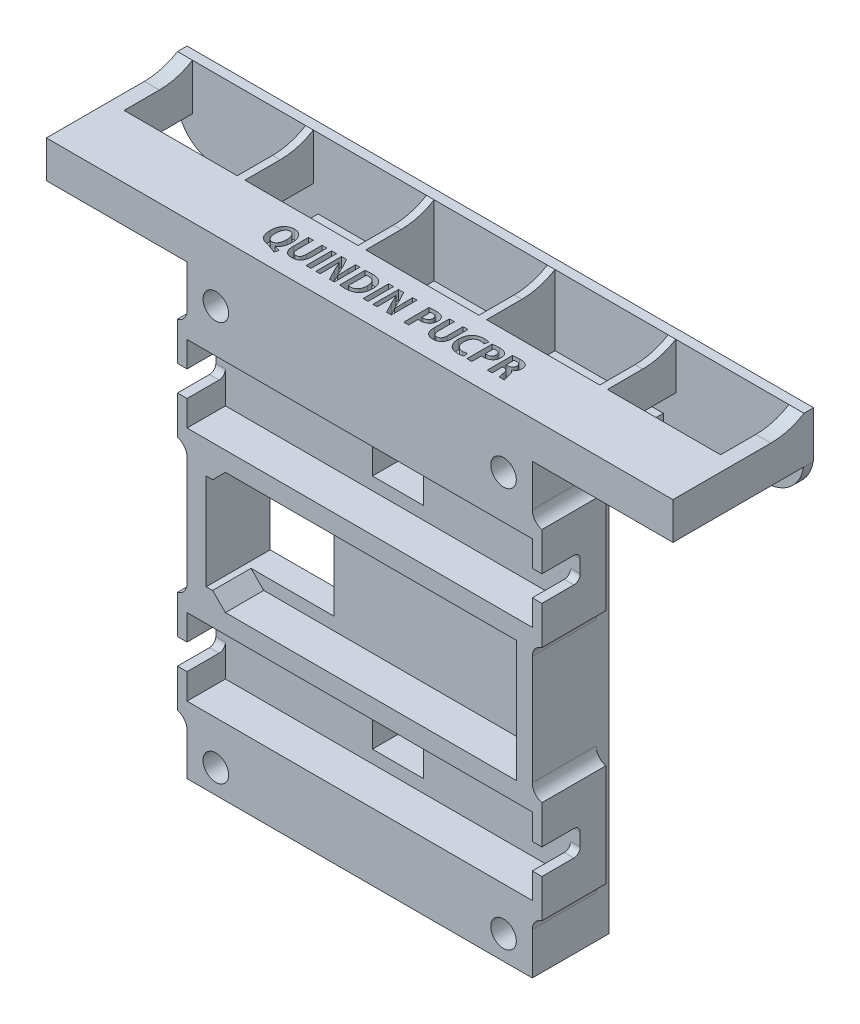
SolidWorks part; units mm, degrees
material "ABS"
ref_plane "Plano frontal" through (0, 0, 0) normal (0, 0, 1) x (1, 0, 0)
ref_plane "Plano superior" through (0, 0, 0) normal (0, 1, 0) x (1, 0, 0)
ref_plane "Plano direito" through (0, 0, 0) normal (1, 0, 0) x (0, 0, -1)
sketch "Esboço1" plane through (0, 0, 0) normal (0, 0, 1) x (1, 0, 0)
  line L0 (-22.1231, 28.35) -> (-22.1231, 2.85) construction
  line L2 (-26.6231, 32.1) -> (-26.6231, 23.6)
  line L3 (-26.6231, -37.9) -> (27.3769, -37.9)
  line L4 (27.3769, 32.1) -> (27.3769, 23.6)
  line L5 (-27.3795, 37.9037) -> (27.3769, -37.9) construction
  line L6 (-26.6231, -37.9) -> (26.6205, 37.8962) construction
  line L7 (-22.1231, 2.85) -> (22.8769, 2.85) construction
  line L8 (22.8769, -34.15) -> (22.8769, -8.65) construction
  line L9 (22.8769, -8.65) -> (-22.1231, -8.65) construction
  line L10 (0.3769, -37.9) -> (0.3769, 37.9) construction
  line L11 (27.3769, 32.1) -> (49.3769, 32.1)
  line L12 (49.3769, 32.1) -> (49.3769, 37.9)
  line L13 (-48.6231, 37.9) -> (49.3769, 37.9)
  line L14 (-48.6231, 37.9) -> (-48.6231, 32.1)
  line L15 (-48.6231, 32.1) -> (-26.6231, 32.1)
  line L33 (27.3769, -29.4) -> (27.3769, -37.9)
  line L35 (-26.6231, -37.9) -> (-26.6231, -29.4)
  line L38 (-28.1231, 15.6) -> (-26.6231, 15.6) construction
  line L39 (-26.6231, -13.4) -> (-28.1231, -13.4)
  line L41 (-26.6231, -29.4) -> (-28.1231, -29.4)
  line L42 (-28.1231, -13.4) -> (-28.1231, -29.4)
  line L43 (-26.6231, 23.6) -> (-28.1231, 23.6)
  line L45 (-26.6231, 7.6) -> (-28.1231, 7.6)
  line L46 (-28.1231, 23.6) -> (-28.1231, 7.6)
  line L47 (27.3769, -29.4) -> (28.8769, -29.4)
  line L48 (-28.1231, -21.4) -> (-26.6231, -21.4) construction
  line L49 (27.3769, -13.4) -> (28.8769, -13.4)
  line L50 (28.8769, -13.4) -> (28.8769, -29.4)
  line L51 (28.8769, 15.6) -> (27.3769, 15.6) construction
  line L52 (28.8769, 23.6) -> (28.8769, 7.6)
  line L53 (27.3769, 7.6) -> (28.8769, 7.6)
  line L54 (27.3769, 23.6) -> (28.8769, 23.6)
  line L55 (-26.6231, 7.6) -> (-26.6231, -13.4)
  line L56 (27.3769, -13.4) -> (27.3769, 7.6)
  line L59 (-48.6231, 32.1) -> (-48.6231, 46.1) construction
  line L60 (49.3769, 32.1) -> (49.3769, 46.1) construction
  circle A0 centre (-22.1231, 28.35) radius 2
  circle A1 centre (22.8769, 28.35) radius 2
  circle A2 centre (22.8769, -34.15) radius 2
  circle A3 centre (-22.1231, -34.15) radius 2
  point P0 (0, 0)
  dimension "D7" = 3.75
  dimension "D8" = 4
  dimension "D11" = 3.75
  dimension "D12" = 4
  dimension "D13" = 4
  dimension "D14" = 4
  dimension "D1" = 54
  dimension "D2" = 75.8
  dimension "D3" = 25.5
  dimension "D4" = 4.5
  dimension "D5" = 11.5
  dimension "D6" = 4.5
  dimension "D9" = 4.5
  dimension "D10" = 4.5
  dimension "D15" = 25.5
  dimension "D16" = 25.5
  dimension "D23" = 45
  dimension "D26" = 5.8
  dimension "D27" = 5.8
  dimension "D28" = 70
  dimension "D29" = 1.5
  dimension "D30" = 1.5
  dimension "D31" = 16
  dimension "D32" = 16
  dimension "D33" = 16.5
  dimension "D34" = 53.5
extrude "Ressalto-extrusão1" add sketch "Esboço1" along normal blind 10
sketch "Esboço7" plane through (0, 0, 0) normal (0, 0, -1) x (-1, 0, 0)
  line L0 (-0.3769, -37.9) -> (-0.3769, 37.9) construction
  line L1 (26.6231, -37.9) -> (-27.3769, -37.9) construction
  line L2 (-49.3769, 37.9) -> (48.6231, 37.9) construction
  line L3 (26.6231, 7.6) -> (26.6231, -13.4) construction
  line L4 (9.6231, 4.6) -> (23.6231, 4.6)
  line L5 (28.6231, 15.6) -> (-29.3769, 15.6) construction
  line L6 (9.6231, 4.6) -> (9.6231, -10.4)
  line L7 (-4.3769, 19.6) -> (3.6231, 19.6)
  line L8 (9.6231, -10.4) -> (23.6231, -10.4)
  line L9 (28.6231, -21.4) -> (-29.3769, -21.4) construction
  line L10 (23.6231, 4.6) -> (23.6231, -10.4)
  line L11 (-4.3769, 19.6) -> (-4.3769, 11.6)
  line L12 (-4.3769, 11.6) -> (3.6231, 11.6)
  line L13 (3.6231, 19.6) -> (3.6231, 11.6)
  line L14 (-4.3769, 19.6) -> (3.6231, 11.6) construction
  line L15 (-4.3769, 11.6) -> (3.6231, 19.6) construction
  line L16 (-4.3769, -17.4) -> (3.6231, -17.4)
  line L17 (-4.3769, -17.4) -> (-4.3769, -25.4)
  line L18 (-4.3769, -25.4) -> (3.6231, -25.4)
  line L19 (3.6231, -17.4) -> (3.6231, -25.4)
  line L20 (-4.3769, -17.4) -> (3.6231, -25.4) construction
  line L21 (-4.3769, -25.4) -> (3.6231, -17.4) construction
  point P18 (-0.3769, 15.6)
  point P23 (-0.3769, -21.4)
  dimension "D1" = 8
  dimension "D2" = 8
  dimension "D3" = 8
  dimension "D4" = 8
  dimension "D5" = 3
  dimension "D6" = 15
  dimension "D7" = 42.5
  dimension "D8" = 14
extrude "Corte-extrusão1" cut sketch "Esboço7" against normal through all
sketch "Esboço9" plane through (0, 0, 10) normal (0, 0, 1) x (1, 0, 0)
  line L0 (29.3769, 15.6) -> (-28.6231, 15.6) construction
  line L1 (27.3769, 9.6) -> (-26.6231, 9.6)
  line L2 (27.3769, 9.6) -> (27.3769, 13.6)
  line L3 (27.3769, 21.6) -> (-26.6231, 21.6)
  line L4 (-26.6231, 9.6) -> (-26.6231, 13.6)
  line L5 (27.3769, -15.4) -> (-26.6231, -15.4)
  line L6 (27.3769, -15.4) -> (27.3769, -19.4)
  line L7 (27.3769, -27.4) -> (-26.6231, -27.4)
  line L8 (-26.6231, -15.4) -> (-26.6231, -19.4)
  line L11 (-26.6231, -23.4) -> (-26.6231, -27.4)
  line L13 (29.3769, -21.4) -> (-28.6231, -21.4) construction
  line L15 (27.3769, -19.4) -> (29.3769, -19.4)
  line L17 (27.3769, -23.4) -> (29.3769, -23.4)
  line L18 (29.3769, -19.4) -> (29.3769, -23.4)
  line L19 (-26.6231, -19.4) -> (-28.6231, -19.4)
  line L21 (-26.6231, -23.4) -> (-28.6231, -23.4)
  line L22 (-28.6231, -19.4) -> (-28.6231, -23.4)
  line L23 (-26.6231, 17.6) -> (-28.6231, 17.6)
  line L25 (-26.6231, 13.6) -> (-28.6231, 13.6)
  line L26 (-28.6231, 17.6) -> (-28.6231, 13.6)
  line L27 (27.3769, 17.6) -> (29.3769, 17.6)
  line L29 (27.3769, 13.6) -> (29.3769, 13.6)
  line L30 (29.3769, 17.6) -> (29.3769, 13.6)
  line L31 (27.3769, -23.4) -> (27.3769, -27.4)
  line L32 (27.3769, 17.6) -> (27.3769, 21.6)
  line L33 (-26.6231, 17.6) -> (-26.6231, 21.6)
  line L34 (-26.6231, -37.9) -> (27.3769, -37.9) construction
  dimension "D1" = 2
  dimension "D2" = 2
  dimension "D3" = 2
  dimension "D4" = 2
  dimension "D5" = 2
  dimension "D6" = 2
  dimension "D7" = 2
  dimension "D8" = 6
  dimension "2" = 2
  dimension "D9" = 6
  dimension "D10" = 16.5
  dimension "D11" = 53.5
  dimension "D12" = 6
  dimension "D13" = 6
extrude "Corte-extrusão7" cut sketch "Esboço9" against normal blind 6
fillet "Filete1" radius 1 8 edges at (-27.3731, -19.4, 4) (-27.3731, -23.4, 4) (-27.3731, 13.6, 4) (-27.3731, 17.6, 4) (28.1269, 13.6, 4) (28.1269, 17.6, 4) (28.1269, -19.4, 4) (28.1269, -23.4, 4)
fillet "Filete2" radius 2 8 edges at (-26.6231, 23.6, 5) (27.3769, 23.6, 5) (27.3769, 7.6, 5) (27.3769, -13.4, 5) (27.3769, -29.4, 5) (-26.6231, -29.4, 5) (-26.6231, -13.4, 5) (-26.6231, 7.6, 5)
sketch "Esboço10" plane through (0, 0, 10) normal (0, 0, 1) x (1, 0, 0)
  line L0 (-26.6231, 9.6) -> (27.3769, 9.6) construction
  line L1 (-18.6231, -12.4) -> (24.8769, -12.4)
  line L2 (-18.6231, -12.4) -> (-18.6231, 6.6)
  line L3 (-18.6231, 6.6) -> (24.8769, 6.6)
  line L4 (24.8769, -12.4) -> (24.8769, 6.6)
  line L5 (-26.6231, 5.6635) -> (-26.6231, -11.4635) construction
  line L6 (27.3769, -11.4635) -> (27.3769, 5.6635) construction
  dimension "D1" = 19
  dimension "D2" = 3
  dimension "D3" = 8
  dimension "D4" = 2.5
extrude "Corte-extrusão8" cut sketch "Esboço10" against normal up to surface (6 mm away) up to face at (0.3769, -21.4, 4)
chamfer "Chanfro1" distance 4 angle 45 2 edges at (-18.6231, 4.6, 7) (-18.6231, -10.4, 7)
sketch "Esboço11" plane through (0, 0, 0) normal (0, 0, -1) x (-1, 0, 0)
  line L0 (48.6231, 32.1) -> (26.6231, 32.1) construction
  line L1 (46.2731, 32.1) -> (28.5731, 32.1)
  line L2 (46.2731, 32.1) -> (46.2731, 37.9)
  line L3 (46.2731, 37.9) -> (28.5731, 37.9)
  line L4 (28.5731, 32.1) -> (28.5731, 37.9)
  line L6 (-49.3769, 37.9) -> (48.6231, 37.9) construction
  line L7 (28.5731, 29.85) -> (28.5731, 39.35) construction
  line L8 (46.2731, 39.35) -> (46.2731, 29.85) construction
  line L10 (27.3731, 37.9) -> (9.6731, 37.9)
  line L11 (27.3731, 37.9) -> (27.3731, 28.35)
  line L12 (27.3731, 28.35) -> (9.6731, 28.35)
  line L13 (9.6731, 37.9) -> (9.6731, 28.35)
  line L14 (8.4731, 37.9) -> (-9.2269, 37.9)
  line L15 (8.4731, 37.9) -> (8.4731, 28.35)
  line L16 (8.4731, 28.35) -> (-9.2269, 28.35)
  line L17 (-9.2269, 37.9) -> (-9.2269, 28.35)
  line L19 (-10.4269, 37.9) -> (-28.1269, 37.9)
  line L20 (-10.4269, 37.9) -> (-10.4269, 28.35)
  line L21 (-10.4269, 28.35) -> (-28.1269, 28.35)
  line L22 (-28.1269, 37.9) -> (-28.1269, 28.35)
  line L23 (-27.3769, 32.1) -> (-49.3769, 32.1) construction
  line L24 (-29.3269, 37.9) -> (-47.0269, 37.9)
  line L25 (-29.3269, 37.9) -> (-29.3269, 32.1)
  line L26 (-29.3269, 32.1) -> (-47.0269, 32.1)
  line L27 (-47.0269, 37.9) -> (-47.0269, 32.1)
  line L28 (-47.0269, 29.85) -> (-47.0269, 39.35) construction
  line L29 (-29.3269, 39.35) -> (-29.3269, 29.85) construction
  line L30 (-28.1269, 39.15) -> (-28.1269, 29.65) construction
  line L31 (-10.4269, 39.15) -> (-10.4269, 29.65) construction
  line L32 (-9.2269, 29.65) -> (-9.2269, 39.15) construction
  line L33 (8.4731, 39.15) -> (8.4731, 29.65) construction
  line L34 (9.6731, 29.65) -> (9.6731, 39.15) construction
  line L35 (27.3731, 39.15) -> (27.3731, 29.65) construction
  line L36 (-30.8269, 28.35) -> (-45.5269, 28.35) construction
  point P26 (-27.3769, 32.1)
extrude "Corte-extrusão9" cut sketch "Esboço11" against normal blind 0.2
sketch "Esboço12" plane through (0, 0, 0) normal (0, 0, -1) x (-1, 0, 0)
  line L0 (8.4731, 37.9) -> (9.6731, 37.9) construction
  line L1 (48.6231, 32.1) -> (46.2731, 32.1)
  line L2 (48.6231, 32.1) -> (48.6231, 37.9)
  line L3 (48.6231, 37.9) -> (46.2731, 37.9)
  line L4 (46.2731, 32.1) -> (46.2731, 37.9)
  line L5 (28.5731, 32.1) -> (27.3731, 32.1)
  line L6 (28.5731, 32.1) -> (28.5731, 37.9)
  line L7 (28.5731, 37.9) -> (27.3731, 37.9)
  line L8 (27.3731, 32.1) -> (27.3731, 37.9)
  line L9 (9.6731, 28.35) -> (8.4731, 28.35)
  line L10 (9.6731, 28.35) -> (9.6731, 37.9)
  line L11 (9.6731, 37.9) -> (8.4731, 37.9)
  line L12 (8.4731, 28.35) -> (8.4731, 37.9)
  line L13 (8.4731, 28.35) -> (8.4731, 37.9) construction
  line L14 (-27.3769, 25.5365) -> (-27.3769, 28.35) construction
  line L15 (-9.2269, 28.35) -> (-10.4269, 28.35)
  line L16 (-9.2269, 28.35) -> (-9.2269, 37.9)
  line L17 (-9.2269, 37.9) -> (-10.4269, 37.9)
  line L18 (-10.4269, 28.35) -> (-10.4269, 37.9)
  line L19 (-28.1269, 32.1) -> (-29.3269, 32.1)
  line L20 (-28.1269, 32.1) -> (-28.1269, 37.9)
  line L21 (-28.1269, 37.9) -> (-29.3269, 37.9)
  line L22 (-29.3269, 32.1) -> (-29.3269, 37.9)
  line L23 (-47.0269, 32.1) -> (-49.3769, 32.1)
  line L24 (-47.0269, 32.1) -> (-47.0269, 37.9)
  line L25 (-47.0269, 37.9) -> (-49.3769, 37.9)
  line L26 (-49.3769, 32.1) -> (-49.3769, 37.9)
  line L27 (26.6231, 28.35) -> (-27.3769, 28.35)
  line L28 (26.6231, 28.35) -> (26.6231, 26.9432)
  line L29 (26.6231, 26.9432) -> (-27.3769, 26.9432)
  line L30 (-27.3769, 28.35) -> (-27.3769, 26.9432)
  line M13 (26.6231, 25.5365) -> (26.6231, 28.35)
  line M14 (26.6231, 28.35) -> (24.1231, 28.35)
  arc M15 (24.1231, 28.35) -> (20.1231, 28.35) centre (22.1231, 28.35) cw
  line M16 (20.1231, 28.35) -> (9.6731, 28.35)
  line M17 (9.6731, 28.35) -> (9.6731, 37.9)
  line M18 (9.6731, 37.9) -> (8.4731, 37.9)
  line M19 (8.4731, 37.9) -> (8.4731, 28.35)
  line M20 (8.4731, 28.35) -> (-9.2269, 28.35)
  line M21 (-9.2269, 28.35) -> (-9.2269, 37.9)
  line M22 (-9.2269, 37.9) -> (-10.4269, 37.9)
  line M23 (-10.4269, 37.9) -> (-10.4269, 28.35)
  line M24 (-10.4269, 28.35) -> (-20.8769, 28.35)
  arc M25 (-20.8769, 28.35) -> (-24.8769, 28.35) centre (-22.8769, 28.35) cw
extrude "Ressalto-extrusão2" add sketch "Esboço12" along normal blind 12 contours L4 L1 L2 L3 | L9 M17 M18 M19 | L29 L9 L15 M15 M16 M20 M24 M25 | L29 L27 M15 | L29 M13 M14 M15 | L15 M21 M22 M23 | L26 L23 L24 L25 | L8 L7 L6 L5 | L29 L30 L27 L28 | L22 L21 L20 L19 region at (-47.4481, 35, 0) region at (0.3769, 27.6435, 0) region at (-9.0731, 33.125, 0) region at (-22.1231, 27.6825, 0) region at (9.8269, 33.125, 0) region at (-25.2778, 27.6223, 0) region at (48.2019, 35, 0)
sketch "Esboço13" plane through (0, 0, -12) normal (0, 0, -1) x (-1, 0, 0)
  line L0 (26.6231, 26.9432) -> (-27.3769, 26.9432) construction
  line L1 (48.6231, 39.35) -> (-49.3769, 39.35)
  line L2 (48.6231, 39.35) -> (48.6231, 32.9432)
  line L3 (42.6231, 26.9432) -> (-43.3769, 26.9432)
  line L4 (-49.3769, 39.35) -> (-49.3769, 32.9432)
  line L5 (44.7731, 39.35) -> (30.0731, 39.35) construction
  line L6 (48.6231, 32.1) -> (48.6231, 37.9) construction
  line L7 (-49.3769, 32.1) -> (-49.3769, 37.9) construction
  arc A0 (48.6231, 32.9432) -> (42.6231, 26.9432) centre (42.6231, 32.9432) cw
  arc A1 (-43.3769, 26.9432) -> (-49.3769, 32.9432) centre (-43.3769, 32.9432) cw
  dimension "D1" = 6
extrude "Ressalto-extrusão3" add sketch "Esboço13" against normal blind 1.5
fillet "Filete4" radius 10 6 edges at (48.2019, 37.9, -10.5) (28.7269, 37.9, -10.5) (9.8269, 37.9, -10.5) (-9.0731, 37.9, -10.5) (-27.9731, 37.9, -10.5) (-47.4481, 37.9, -10.5)
sketch "Esboço14" plane through (0, 26.9432, 0) normal (0, -1, 0) x (1, 0, 0)
  line L0 (27.3769, -10.5) -> (27.3769, 0) construction
  line L1 (27.3769, -7.75) -> (-26.6231, -7.75)
  line L2 (27.3769, -7.75) -> (27.3769, -3.5)
  line L3 (27.3769, -3.5) -> (-26.6231, -3.5)
  line L4 (-26.6231, -7.75) -> (-26.6231, -3.5)
  line L5 (-26.6231, -10.5) -> (-26.6231, 0) construction
  line L6 (-42.6231, -12) -> (43.3769, -12) construction
  point P8 (-26.6231, -3.2299)
  dimension "D1" = 4.25
  dimension "D2" = 4.25
extrude "Corte-extrusão10" cut sketch "Esboço14" against normal up to surface (1.4068 mm away) and the other way through all up to face at (0.3769, 28.35, -5.15)
fillet "Filete5" radius 1 4 edges at (-9.0731, 28.35, -7.75) (-9.0731, 28.35, -3.5) (9.8269, 28.35, -7.75) (9.8269, 28.35, -3.5)
sketch "Esboço15" plane through (0, 37.9, 0) normal (0, 1, 0) x (1, 0, 0)
  text T0 "QUINDIN PUCPR" font "@Adobe Gothic Std B" height 4
extrude "Corte-extrusão11" cut sketch "Esboço15" against normal blind 1.5
sketch "Esboço16" plane through (0, 0, 0) normal (0, 0, -1) x (-1, 0, 0)
  line L0 (26.6231, -31.3365) -> (26.6231, -37.9) construction
  line L1 (-27.3769, -37.9) -> (26.6231, -37.9)
  line L2 (-27.3769, -37.9) -> (-27.3769, -36.9)
  line L3 (-27.3769, -36.9) -> (26.6231, -36.9)
  line L4 (26.6231, -37.9) -> (26.6231, -36.9)
  line L5 (-24.2985, 26.9432) -> (-27.3769, 26.9432) construction
  line L6 (-27.3769, -36.9) -> (-26.3769, -36.9)
  line L7 (-27.3769, -36.9) -> (-27.3769, 26.9432)
  line L8 (-27.3769, 26.9432) -> (-26.3769, 26.9432)
  line L9 (-26.3769, -36.9) -> (-26.3769, 26.9432)
  line L10 (26.6231, 26.9432) -> (23.5448, 26.9432) construction
  line L11 (26.6231, -36.9) -> (25.6231, -36.9)
  line L12 (26.6231, -36.9) -> (26.6231, 26.9432)
  line L13 (26.6231, 26.9432) -> (25.6231, 26.9432)
  line L14 (25.6231, -36.9) -> (25.6231, 26.9432)
  line M24 (-24.2985, 26.9432) -> (-27.3769, 26.9432)
  line M25 (-27.3769, 26.9432) -> (-27.3769, 25.5365)
  line M29 (-27.3769, 5.6635) -> (-27.3769, -11.4635)
  line M33 (-27.3769, -31.3365) -> (-27.3769, -37.9)
  line M34 (-27.3769, -37.9) -> (26.6231, -37.9)
  line M35 (26.6231, -37.9) -> (26.6231, -31.3365)
  dimension "D1" = 1
  dimension "D2" = 1
  dimension "D3" = 1
extrude "Ressalto-extrusão4" add sketch "Esboço16" along normal blind 2 contours L3 M33 M34 M35 | L3 L9 L7 M24 M25 M29 M33 | L11 L14 L13 L12 region at (0.3769, -37.4, 0) region at (26.8769, -4.9784, 0)
